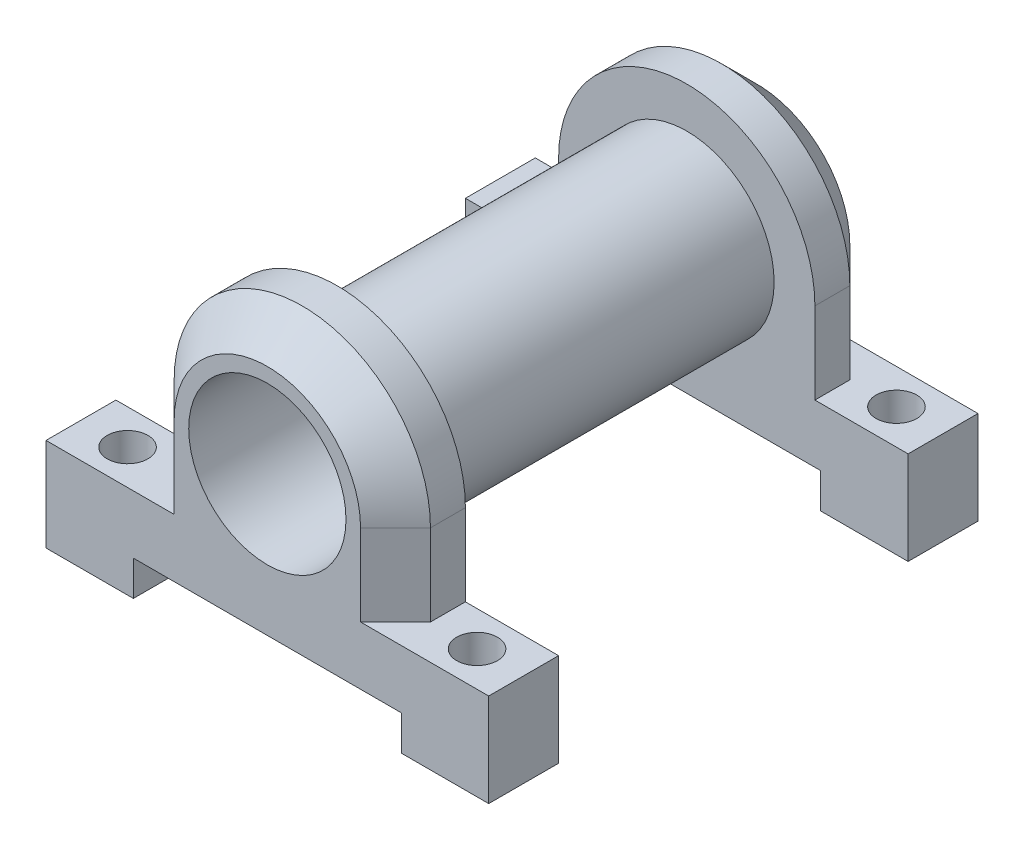
SolidWorks part; units mm, degrees
ref_plane "Front Plane" through (0, 0, 0) normal (0, 0, 1) x (1, 0, 0)
ref_plane "Top Plane" through (0, 0, 0) normal (0, 1, 0) x (1, 0, 0)
ref_plane "Right Plane" through (0, 0, 0) normal (1, 0, 0) x (0, 0, -1)
sketch "Sketch1" plane through (0, 0, 0) normal (0, 0, 1) x (1, 0, 0)
  line L0 (-11, 0) -> (-11, -7)
  line L1 (-11, -15) -> (11, -15)
  line L2 (11, -7) -> (11, 0)
  line L3 (-11, -7) -> (11, -7) construction
  line L4 (-11, -15) -> (-19, -15)
  line L6 (-11, -7) -> (-19, -7)
  line L7 (-19, -15) -> (-19, -7)
  line L8 (11, -15) -> (19, -15)
  line L10 (11, -7) -> (19, -7)
  line L11 (19, -15) -> (19, -7)
  line L12 (-11, 0) -> (11, 0) construction
  line L13 (-11, -7) -> (-11, -15) construction
  line L14 (11, -7) -> (11, -15) construction
  arc A0 (11, 0) -> (-11, 0) centre (0, 0) ccw
  dimension "D1" = 22
  dimension "D2" = 15
  dimension "D3" = 8
  dimension "D4" = 8
extrude "Boss-Extrude1" add sketch "Sketch1" along normal blind 6
sketch "Sketch2" plane through (0, 0, 6) normal (0, 0, 1) x (1, 0, 0)
  circle A0 centre (0, 0) radius 7.5
  dimension "D1" = 15
extrude "Boss-Extrude2" add sketch "Sketch2" along normal blind 30
sketch "Sketch3" plane through (0, 0, 36) normal (0, 0, 1) x (1, 0, 0)
  line L3 (-11, 0) -> (-11, -7)
  line L4 (-19, -15) -> (19, -15)
  line L5 (11, -7) -> (11, 0)
  line L6 (-11, 0) -> (-11, -7)
  line L7 (-19, -15) -> (19, -15)
  line L8 (11, -7) -> (11, 0)
  line L13 (-19, -7) -> (-19, -15)
  line L14 (-19, -7) -> (-19, -15)
  line L15 (19, -15) -> (19, -7)
  line L16 (19, -15) -> (19, -7)
  line L17 (19, -7) -> (11, -7)
  line L18 (19, -7) -> (11, -7)
  line L19 (-11, -7) -> (-19, -7)
  line L20 (-11, -7) -> (-19, -7)
  arc A2 (11, 0) -> (-11, 0) centre (0, 0) ccw
  arc A3 (11, 0) -> (-11, 0) centre (0, 0) ccw
  dimension "D1" = 0
extrude "Boss-Extrude3" add sketch "Sketch3" along normal blind 6
sketch "Sketch4" plane through (0, 0, 42) normal (0, 0, 1) x (1, 0, 0)
  circle A0 centre (0, 0) radius 6.75
  dimension "D1" = 13.5
extrude "Cut-Extrude1" cut sketch "Sketch4" against normal through all
sketch "Sketch5" plane through (0, 0, 0) normal (0, 0, -1) x (-1, 0, 0)
  line L0 (19, -15) -> (-19, -15) construction
  line L1 (-11.5, -15) -> (11.5, -15)
  line L2 (-11.5, -15) -> (-11.5, -12)
  line L3 (-11.5, -12) -> (11.5, -12)
  line L4 (11.5, -15) -> (11.5, -12)
  line L5 (0, -12) -> (0, 0) construction
  dimension "D1" = 23
  dimension "D2" = 3
extrude "Cut-Extrude2" cut sketch "Sketch5" against normal through all and the other way through all
sketch "Sketch6" plane through (0, -7, 0) normal (0, 1, 0) x (1, 0, 0)
  line L0 (-15, -3) -> (15, -3) construction
  line L1 (19, -42) -> (11, -42) construction
  line L3 (0, -3) -> (0, 0) construction
  circle A0 centre (-15, -3) radius 1.75
  circle A1 centre (15, -3) radius 1.75
  circle A2 centre (15, -39) radius 1.75
  circle A3 centre (-15, -39) radius 1.75
  dimension "D3" = 3.5
  dimension "D1" = 30
  dimension "D2" = 3
  dimension "D5" = 3
  dimension "D4" = 2
extrude "Cut-Extrude3" cut sketch "Sketch6" against normal through all
chamfer "Chamfer1" distance 3 angle 45 6 edges at (11, -3.5, 42) (0, 11, 42) (-11, -3.5, 42) (11, -3.5, 0) (0, 11, 0) (-11, -3.5, 0)
